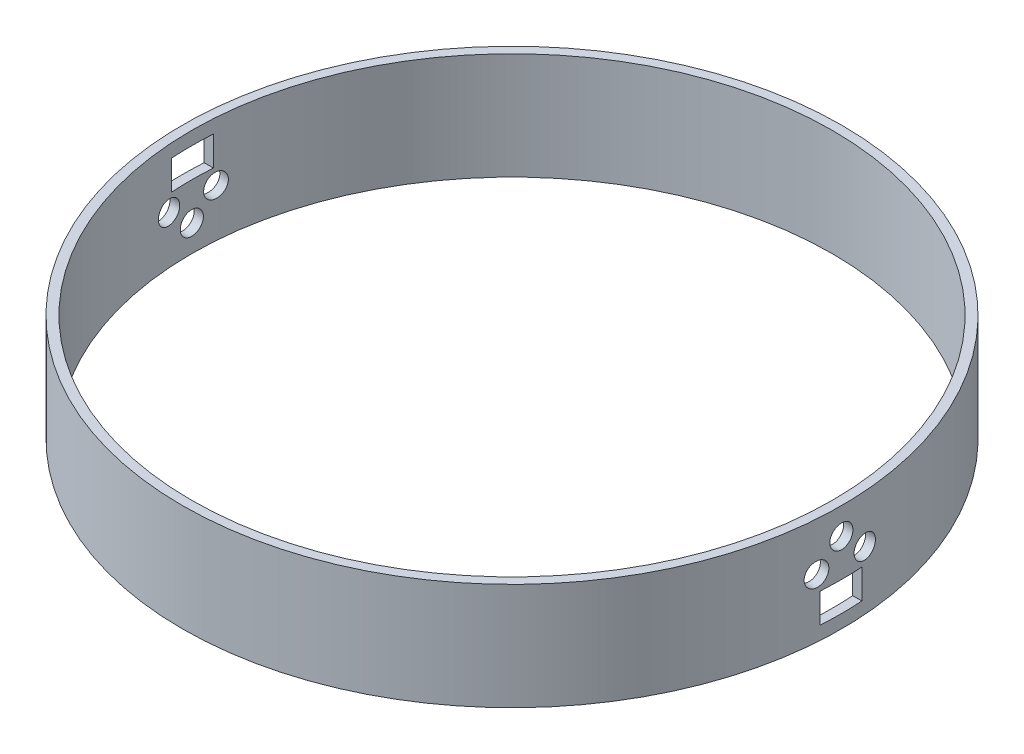
SolidWorks part; units mm, degrees
material "A-Glass Fiber"
ref_plane "Front Plane" through (0, 0, 0) normal (0, 0, 1) x (1, 0, 0)
ref_plane "Top Plane" through (0, 0, 0) normal (0, 1, 0) x (1, 0, 0)
ref_plane "Right Plane" through (0, 0, 0) normal (1, 0, 0) x (0, 0, -1)
sketch "Sketch1" plane through (0, 0, 0) normal (0, 1, 0) x (1, 0, 0)
  circle A0 centre (0, 0) radius 78.359
  circle A1 centre (0, 0) radius 76.1746
  dimension "D1" = 156.718
  dimension "D2" = 152.3492
extrude "Boss-Extrude1" add sketch "Sketch1" along normal blind 25.4
sketch "Sketch2" plane through (0, 0, 0) normal (1, 0, 0) x (0, 0, -1)
  line L0 (-78.359, 0) -> (78.359, 0) construction
  line L1 (-5, 3.175) -> (5, 3.175)
  line L2 (-5, 3.175) -> (-5, 10.175)
  line L3 (-5, 10.175) -> (5, 10.175)
  line L4 (5, 3.175) -> (5, 10.175)
  line L5 (-5, 3.175) -> (5, 10.175) construction
  line L6 (-5, 10.175) -> (5, 3.175) construction
  circle A0 centre (0, 19.065) radius 2.75
  point P0 (0, 6.675)
  dimension "D4" = 5.5
  dimension "D1" = 10
  dimension "D2" = 7
  dimension "D3" = 3.175
  dimension "D5" = 8.89
extrude "Cut-Extrude1" cut sketch "Sketch2" along normal through all
ref_plane "Plane1" through (0, 0, 0) normal (0.9973, 0, 0.0728) x (0, -1, 0)
sketch "Sketch5" plane through (0, 0, 0) normal (0.9973, 0, 0.0728) x (0, -1, 0)
  line L0 (-10.175, 0.7076) -> (-10.175, 10.681) construction
  circle A0 centre (-13.985, 0) radius 2.75
  dimension "D1" = 5.5
  dimension "D2" = 3.81
extrude "Cut-Extrude2" cut sketch "Sketch5" along normal through all
pattern_circular "CirPattern1" count 2 every 8.407 about axis through (0, 25.4, 0) along (0, 1, 0) of "Cut-Extrude2"
sketch "Sketch8" plane through (0, 0, 0) normal (1, 0, 0) x (0, 0, -1)
  line L0 (0, 25.4) -> (0, 0) construction
  line L1 (5, 15.225) -> (-5, 15.225)
  line L2 (5, 15.225) -> (5, 22.225)
  line L3 (5, 22.225) -> (-5, 22.225)
  line L4 (-5, 15.225) -> (-5, 22.225)
  line L5 (5, 15.225) -> (-5, 22.225) construction
  line L6 (5, 22.225) -> (-5, 15.225) construction
  line L8 (78.359, 25.4) -> (-78.359, 25.4) construction
  circle A0 centre (0, 6.335) radius 2.75
  point P0 (0, 18.725)
  dimension "D4" = 5.5
  dimension "D3" = 3.175
  dimension "D5" = 8.89
  dimension "D1" = 10
  dimension "D2" = 7
extrude "Cut-Extrude3" cut sketch "Sketch8" against normal through all
sketch "Sketch9" plane through (0, 0, 0) normal (0.9973, 0, 0.0728) x (0, -1, 0)
  line L0 (-15.225, -0.7076) -> (-15.225, -10.681) construction
  line L1 (-25.4, 0) -> (0, 0) construction
  circle A0 centre (-11.415, 0) radius 2.75
  dimension "D1" = 5.5
  dimension "D2" = 3.81
extrude "Cut-Extrude4" cut sketch "Sketch9" against normal through all
pattern_circular "CirPattern2" count 2 every 8.41 about axis through (0, 25.4, 0) along (0, 1, 0) of "Cut-Extrude4"
equation "\"Mid_Tube_Length\"= 1in"
equation "\"Bodytube_OD\"= 6.17in"
equation "\"Bodytube_ID\"= 5.998in"
equation "\"D1@Sketch1\"=\"Bodytube_OD\""
equation "\"D2@Sketch1\"= \"Bodytube_ID\""
equation "\"Camera_Cutout_Width\"=10mm"
equation "\"Camera_Cutout_Height\"=7mm"
equation "\"Fwd_Tube_Length\"= 40in"
equation "\"BKHD_Screw_Diam\"= 3.5mm"
equation "\"Fwd_BKHD_From_Top\"= 18in"
equation "\"Shear_Screw_Diameter\"= 0.086in"
equation "\"Shear_Screw_Coupler_Location\"= 4.5in"
equation "\"Motor_OD\"= 4in"
equation "\"Mid_Coupler_Length\"= 13in"
equation "\"Aft_Section_Length\"= 39in"
equation "\"AB_Coupler_OD_Length\"= 1in"
equation "\"AB_Coupling_Section_Length\"= 0.375in"
equation "\"AB_Coupler_Length\"= \"AB_Coupler_OD_Length\" + \"AB_Coupling_Section_Length\" * 2"
equation "\"Cutout_Angle\"= 80"
equation "\"AB_Paddle_Height\"= 0.375in"
equation "\"AB_Coupler_Num_Screws\"= 4"
equation "\"AB_BKHD_Thickness\"= 0.375in"
equation "\"AB_Mount_From_Bottom\"= 23.175in"
equation "\"Num_Cutouts\"= 3"
equation "\"AB_Coupler_OD\"= 6.17in"
equation "\"AB_Coupler_ID\"= 5.75in"
equation "\"AB_Coupler_Surface_Diameter\"= 5.998in"
equation "\"AB_Coupling_Screw_Diameter\"= 0.15748in"
equation "\"AB_Central_Bushing_Length\"= .4724in"
equation "\"Lead_Screw_Dist\"= 3.4in"
equation "\"Lead_Screw_Diam\"= 0.386in"
equation "\"Lead_Screw_Length\"= (\"Mid_Coupler_Length\" + 2*0.375in + 2*0.5in)"
equation "\"Paddle_Pin_Offset\"= .25in"
equation "\"Paddle_Pin_Radius\"= 2.25in"
equation "\"SS_Paddle_Pin_Radius\"= 2.25*0.66in"
equation "\"Paddle_Gear_OD\"= 3.2in"
equation "\"Drive_Gear_OD\"= 1.7in"
equation "\"Fin_Thickness\"= .118in"
equation "\"Guiderail_Cutout_Diameter\"= 1.5in"
equation "\"DB9_Hole_Dist\"= 25mm"
equation "\"DB9_Relief_Width\"= 0.47in"
equation "\"DB9_Relief_Hole_Offset\"= 0.09in"
equation "\"Airbrakes_Wire_Hole_Dia\"= .25in"
equation "\"Airbrakes_Wire_Hole_Dist\"= 1.1in"
equation "\"Servo_Gear_Offset\"= 0.5in"
equation "\"FWD_Shear_Screw_Dist\"= 1.5in"
equation "\"D2@Sketch2\"=\"Camera_Cutout_Height\""
equation "\"D1@Sketch2\"=\"Camera_Cutout_Width\""
equation "\"Camera_Screw_Dia\"= 0.216535"
equation "\"D4@Sketch2\"=\"Camera_Screw_Dia\""
equation "\"D1@Sketch5\"=\"Camera_Screw_Dia\""
equation "\"Camera_Hole_Angle\"= atn ( 2 / 3 * tan ( 12.5deg ) )"
equation "\"D2@CirPattern1\"=\"Camera_Hole_Angle\""
equation "\"D4@Sketch8\"=\"Camera_Screw_Dia\""
equation "\"D1@Sketch9\"=\"Camera_Screw_Dia\""
